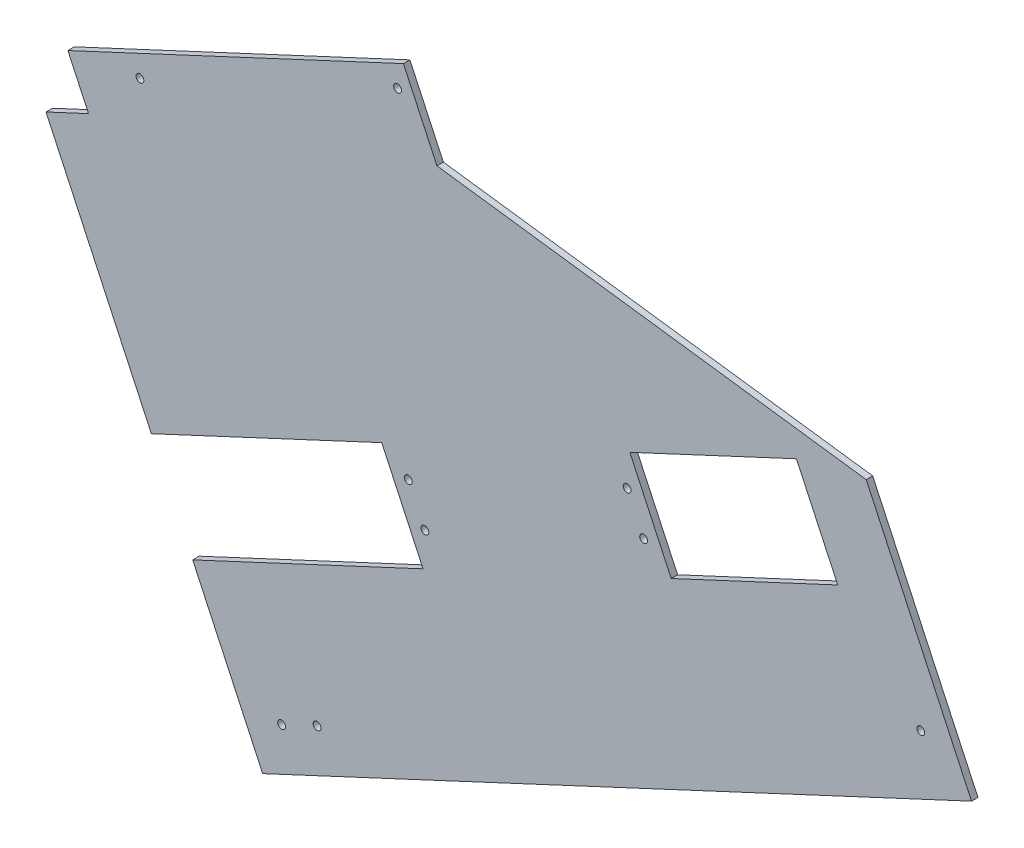
SolidWorks part; units mm, degrees
material "Balsa"
ref_plane "Front Plane" through (0, 0, 0) normal (0, 0, 1) x (1, 0, 0)
ref_plane "Top Plane" through (0, 0, 0) normal (0, 1, 0) x (1, 0, 0)
ref_plane "Right Plane" through (0, 0, 0) normal (1, 0, 0) x (0, 0, -1)
sketch "Sketch1" plane through (0, 0, 0) normal (0, 0, 1) x (1, 0, 0)
  line L0 (344.8461, -37.3321) -> (125.2807, -8.1077)
  line L1 (125.2807, -8.1077) -> (108.169, 28.5884)
  line L2 (108.169, 28.5884) -> (-63.4467, -51.4373)
  line L3 (-63.4467, -51.4373) -> (57.9293, -311.7289) construction
  line L4 (57.9293, -311.7289) -> (398.701, -152.8244)
  line L5 (271.5352, 119.8836) -> (277.3251, 107.4672) construction
  line L6 (190.5834, 136.311) -> (-12.0446, 41.824) construction
  line L7 (-63.4467, -51.4373) -> (255.5737, 97.3243) construction
  line L8 (398.701, -152.8244) -> (344.8461, -37.3321)
  line L9 (57.9293, -311.7289) -> (36.1779, -321.8717)
  line L10 (36.1779, -321.8717) -> (-74.6326, -84.2378)
  line L12 (-74.6326, -84.2378) -> (-52.8812, -74.095)
  line L13 (-90.9879, -49.1637) -> (-85.1981, -61.5801) construction
  line L14 (-52.8812, -74.095) -> (-63.4467, -51.4373)
  line L15 (50.7481, 1.8126) -> (339.9495, -36.6803) construction
  circle A0 centre (162.7613, -40.6644) radius 32.5 construction
  circle A1 centre (336.0773, -108.8767) radius 32.5 construction
  circle A2 centre (90.1802, -40.6644) radius 32.5 construction
  circle A3 centre (232.5481, -40.6644) radius 32.5 construction
  circle A4 centre (207.2768, 100.5118) radius 39.5 construction
  arc A5 (-3.3339, 41.4724) -> (-17.3744, 34.9252) centre (-8.0297, 33.2141) ccw construction
  circle A6 centre (304.5287, -40.6644) radius 32.5 construction
  circle A7 centre (254.9584, -108.8767) radius 32.5 construction
  circle A8 centre (179.3206, -108.8767) radius 32.5 construction
  circle A9 centre (101.4264, -108.8767) radius 32.5 construction
  circle A10 centre (270.383, -163.8108) radius 32.5 construction
  circle A11 centre (372.7594, -134.5783) radius 2
  dimension "D2" = 65
  dimension "D3" = 65
  dimension "D5" = 4
  dimension "D1" = 350
  dimension "D4" = 25
  dimension "24.5/2" = 15.8
  dimension "D6" = 27.5
extrude "Boss-Extrude1" add sketch "Sketch1" along normal up to surface (3.3 mm away)
sketch "Sketch2" plane through (0, 0, 3.3) normal (0, 0, 1) x (1, 0, 0)
  circle A0 centre (105.1447, 16.1444) radius 2
  circle A1 centre (-26.5934, -45.2861) radius 2
  circle A2 centre (-26.5934, -45.2861) radius 2 construction
  circle A3 centre (105.1447, 16.1444) radius 2 construction
extrude "Cut-Extrude1" cut sketch "Sketch2" against normal through all
sketch "Sketch3" plane through (0, 0, 3.3) normal (0, 0, 1) x (1, 0, 0)
  line L2 (398.701, -152.8244) -> (36.1779, -321.8717) construction
  line L3 (36.1779, -321.8717) -> (-74.6326, -84.2378) construction
  circle A0 centre (45.8517, -295.2932) radius 2
  circle A1 centre (63.9779, -286.8408) radius 2
  dimension "D1" = 4
  dimension "D2" = 4
  dimension "D3" = 20
  dimension "D5" = 20
  dimension "D6" = 20
  dimension "D4" = 20
extrude "Cut-Extrude2" cut sketch "Sketch3" against normal blind 4
sketch "Sketch4" plane through (0, 0, 3.3) normal (0, 0, 1) x (1, 0, 0)
  line L0 (330.2782, -91.2744) -> (309.1473, -45.959)
  line L1 (309.1473, -45.959) -> (223.9543, -85.6851)
  line L2 (223.9543, -85.6851) -> (245.0853, -131.0005)
  line L3 (245.0853, -131.0005) -> (330.2782, -91.2744)
  line L4 (309.1473, -45.959) -> (223.9543, -85.6851) construction
  line L5 (245.0853, -131.0005) -> (330.2782, -91.2744) construction
  line L6 (330.2782, -91.2744) -> (309.1473, -45.959) construction
  line L7 (118.2022, -190.1671) -> (97.0712, -144.8517)
  line L8 (97.0712, -144.8517) -> (-20.7488, -199.7921)
  line L9 (-20.7488, -199.7921) -> (0.3821, -245.1075)
  line L10 (0.3821, -245.1075) -> (118.2022, -190.1671)
  line L11 (118.2022, -190.1671) -> (0.3821, -245.1075) construction
  line L12 (-20.7488, -199.7921) -> (97.0712, -144.8517) construction
  line L13 (97.0712, -144.8517) -> (118.2022, -190.1671) construction
extrude "Cut-Extrude3" cut sketch "Sketch4" against normal blind 10
sketch "Sketch5" plane through (0, 0, 3.3) normal (0, 0, 1) x (1, 0, 0)
  circle A0 centre (231.009, -120.4069) radius 2
  circle A1 centre (222.5566, -102.2807) radius 2
  circle A2 centre (119.135, -172.5746) radius 2
  circle A3 centre (110.6826, -154.4484) radius 2
  circle A4 centre (119.135, -172.5746) radius 2 construction
  circle A7 centre (110.6826, -154.4484) radius 2 construction
  circle A8 centre (222.5566, -102.2807) radius 2 construction
  circle A9 centre (231.009, -120.4069) radius 2 construction
extrude "Cut-Extrude4" cut sketch "Sketch5" against normal blind 10
